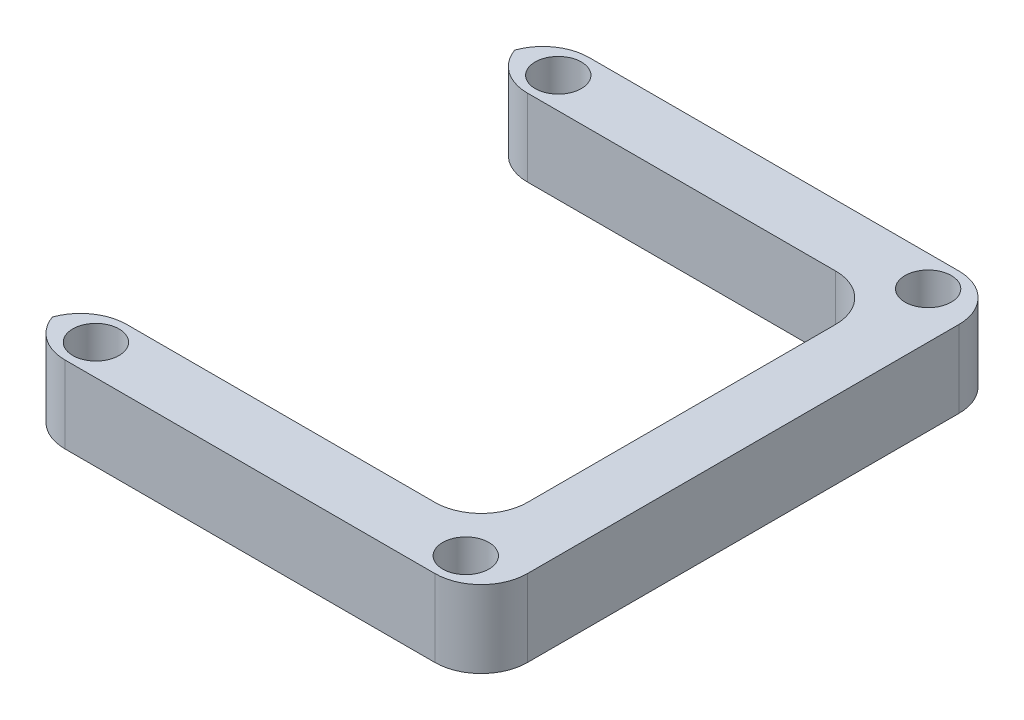
SolidWorks part; units mm, degrees
ref_plane "Front Plane" through (0, 0, 0) normal (0, 0, 1) x (1, 0, 0)
ref_plane "Top Plane" through (0, 0, 0) normal (0, 1, 0) x (1, 0, 0)
ref_plane "Right Plane" through (0, 0, 0) normal (1, 0, 0) x (0, 0, -1)
sketch "Sketch1" plane through (0, 0, 0) normal (0, 1, 0) x (1, 0, 0)
  line L0 (0, 4) -> (26, 4)
  line L1 (0, 0) -> (30, 0)
  line L2 (0, 0) -> (0, 4)
  line L3 (0, 34) -> (30, 34)
  line L4 (30, 0) -> (30, 34)
  line L5 (26, 4) -> (26, 30)
  line L6 (26, 30) -> (0, 30)
  line L7 (0, 0) -> (0, 4)
  line L8 (0, 30) -> (0, 34)
  line L9 (0, 30) -> (0, 34)
  circle A0 centre (3, 2) radius 1.5
  circle A1 centre (3, 32) radius 1.5
  circle A2 centre (27, 32) radius 1.5
  circle A3 centre (27, 2) radius 1.5
  dimension "D6" = 3
  dimension "D7" = 3
  dimension "D8" = 3
  dimension "D9" = 3
  dimension "D1" = 30
  dimension "D2" = 34
  dimension "D3" = 4
  dimension "D4" = 4
  dimension "D5" = 4
  dimension "D10" = 30
  dimension "D11" = 30
  dimension "D12" = 24
  dimension "D13" = 24
  dimension "D14" = 3
  dimension "D15" = 2
  dimension "D16" = 2
extrude "Boss-Extrude1" add sketch "Sketch1" along normal blind 5 contours L8 L6 L5 L0 L2 L1 L4 L3 A3 A2 A1 A0 region at (13, 0, -3.5466)
fillet "Fillet2" radius 3 8 edges at (30, 2.5, -34) (0, 2.5, -34) (0, 2.5, -30) (26, 2.5, -30) (26, 2.5, -4) (0, 2.5, -4) (0, 2.5, 0) (30, 2.5, 0)
